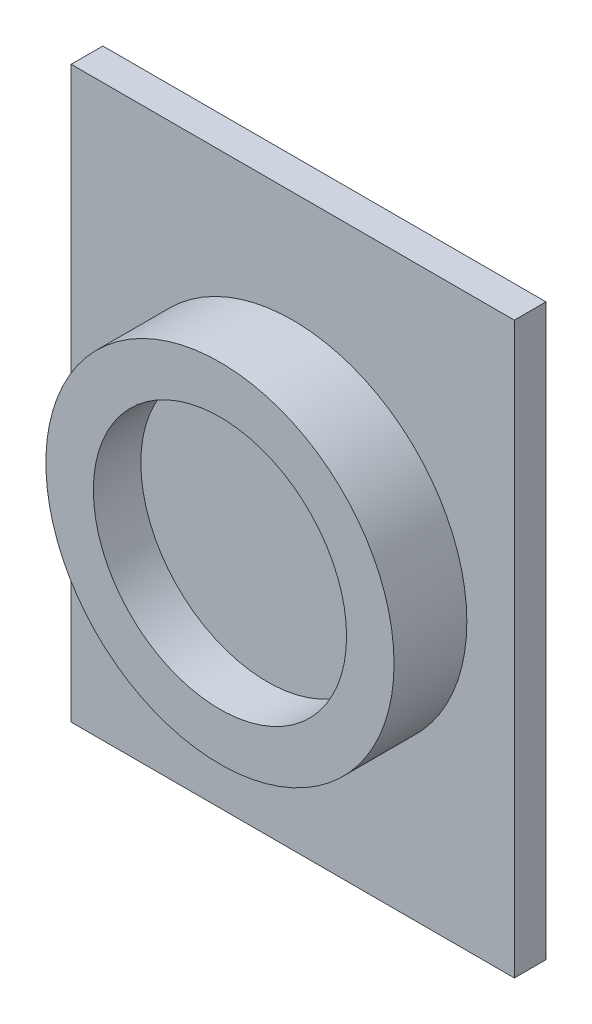
SolidWorks part; units mm, degrees
ref_plane "Alzado" through (0, 0, 0) normal (0, 0, 1) x (1, 0, 0)
ref_plane "Planta" through (0, 0, 0) normal (0, 1, 0) x (1, 0, 0)
ref_plane "Vista lateral" through (0, 0, 0) normal (1, 0, 0) x (0, 0, -1)
sketch "Croquis1" plane through (0, 0, 0) normal (0, 0, 1) x (1, 0, 0)
  line L0 (0, 0) -> (140, 0)
  line L1 (140, 0) -> (140, 180)
  line L2 (140, 180) -> (0, 180)
  line L3 (0, 180) -> (0, 0)
  line L4 (0, 180) -> (140, 0) construction
  line L5 (140, 180) -> (0, 0) construction
  dimension "D1" = 140
  dimension "D2" = 180
extrude "Saliente-Extruir1" add sketch "Croquis1" along normal blind 10
sketch "Croquis2" plane through (0, 0, 10) normal (0, 0, 1) x (1, 0, 0)
  line L0 (0, 180) -> (140, 0) construction
  line L1 (0, 0) -> (140, 0) construction
  line L2 (140, 180) -> (0, 0) construction
  circle A0 centre (70, 90) radius 55
extrude "Saliente-Extruir2" add sketch "Croquis2" along normal blind 8
sketch "Croquis3" plane through (0, 0, 18) normal (0, 0, 1) x (1, 0, 0)
  circle A0 centre (70, 90) radius 40
  circle A1 centre (70, 90) radius 55
extrude "Saliente-Extruir3" add sketch "Croquis3" along normal blind 15
ref_plane "Plano1" through (140, 180, 0) normal (0, 1, 0) x (1, 0, 0)
